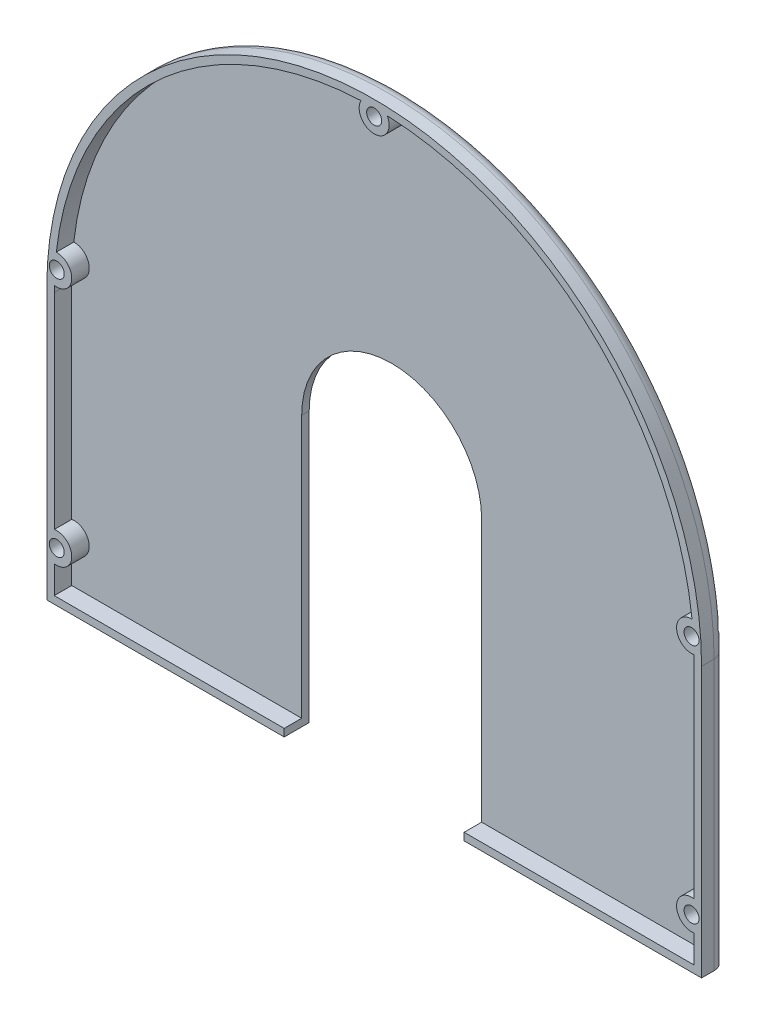
SolidWorks part; units mm, degrees
ref_plane "Front Plane" through (0, 0, 0) normal (0, 0, 1) x (1, 0, 0)
ref_plane "Top Plane" through (0, 0, 0) normal (0, 1, 0) x (1, 0, 0)
ref_plane "Right Plane" through (0, 0, 0) normal (1, 0, 0) x (0, 0, -1)
sketch "Sketch3" plane through (0, 0, 0) normal (0, 0, 1) x (1, 0, 0)
  line L1 (-65.5, 27) -> (65.5, 27)
  line L2 (-65.5, 27) -> (-65.5, -27)
  line L3 (-65.5, -27) -> (65.5, -27)
  line L4 (65.5, 27) -> (65.5, -27)
  line L5 (-65.5, 27) -> (65.5, -27) construction
  line L6 (-65.5, -27) -> (65.5, 27) construction
  arc A1 (65.5, 27) -> (-65.5, 27) centre (0, 27) ccw
  point P0 (0, 0)
  dimension "D1" = 131
  dimension "D2" = 54
extrude "Boss-Extrude2" add sketch "Sketch3" along normal blind 5 contours L1 A1 | L4 L1 L2 L3
hole_wizard "Ø3.0 (3) Diameter Hole1" positions "Sketch4" profile "Sketch5" hole size "Ø3.0" standard "AS"
sketch "Sketch4" plane through (0, 0, 5) normal (0, 0, 1) x (1, 0, 0)
  line L0 (-65.5, -27) -> (65.5, -27) construction
  line L1 (-65.5, 27) -> (-65.5, -27) construction
  line L2 (65.5, 27) -> (65.5, -27) construction
  arc A1 (65.5, 27) -> (-65.5, 27) centre (0, 27) ccw construction
  point P0 (-63.5, -17)
  point P2 (63.5, -17)
  point P4 (0, 89.5)
  point P6 (63.5, 31.2101)
  point P8 (-63.5, 31.2101)
  dimension "D1" = 10
  dimension "D2" = 2
  dimension "D3" = 2
  dimension "D4" = 2
  dimension "D5" = 2
  dimension "D6" = 10
  dimension "D7" = 62.5
sketch "Sketch5" plane through (-63.5, -17, 5) normal (1, 0, 0) x (0, -1, 0)
  line L0 (0, 0) -> (0, 20.9013)
  line L1 (0, 20.9013) -> (1.5, 20)
  line L2 (1.5, 20) -> (1.5, 0)
  line L5 (1.5, 0) -> (0, 0)
  line L10 (0, 20.9013) -> (-1.5, 20) construction
  line L11 (0, -6.35) -> (0, 107.95) construction
  dimension "Hole Dia." = 3
  dimension "Hole Depth" = 20
  dimension "Drill Angle" = 118
shell "Shell1" thickness 1.5
sketch "Sketch6" plane through (0, 0, 0) normal (0, 0, -1) x (-1, 0, 0)
  line L0 (-18, 27) -> (-18, -27)
  line L1 (65.5, -27) -> (-65.5, -27) construction
  line L3 (18, -27) -> (18, 27)
  line L4 (-18, -27) -> (18, -27)
  arc A0 (18, 27) -> (-18, 27) centre (0, 27) ccw
  dimension "D1" = 36
extrude "Cut-Extrude1" cut sketch "Sketch6" against normal through all
fillet "Fillet2" radius 2.5 3 edges at (65.5, 0, 0) (-65.5, 0, 0) (0, 92.5, 0)
